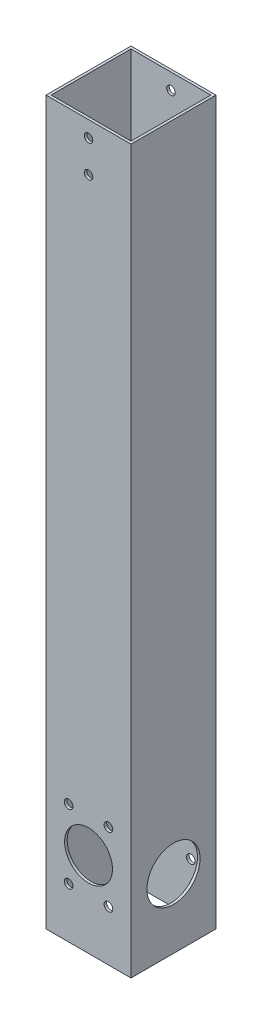
SolidWorks part; units mm, degrees
material "6061 Alloy"
ref_plane "Front Plane" through (0, 0, 0) normal (0, 0, 1) x (1, 0, 0)
ref_plane "Top Plane" through (0, 0, 0) normal (0, 1, 0) x (1, 0, 0)
ref_plane "Right Plane" through (0, 0, 0) normal (1, 0, 0) x (0, 0, -1)
sketch "Sketch1" plane through (0, 0, 0) normal (0, 1, 0) x (1, 0, 0)
  line L1 (25.4, 25.4) -> (-25.4, 25.4)
  line L2 (25.4, 25.4) -> (25.4, -25.4)
  line L3 (25.4, -25.4) -> (-25.4, -25.4)
  line L4 (-25.4, 25.4) -> (-25.4, -25.4)
  line L5 (25.4, 25.4) -> (-25.4, -25.4) construction
  line L6 (25.4, -25.4) -> (-25.4, 25.4) construction
  point P0 (0, 0)
  dimension "D1" = 50.8
extrude "Extrude-Thin1" add sketch "Sketch1" along normal blind 431.8 thin thin type one direction reverse wall 1.524
sketch "Sketch2" plane through (0, 0, 0) normal (0, 0, 1) x (1, 0, 0)
  line L0 (-36.2563, 68.2625) -> (38.5702, 68.2625) construction
  line L1 (-25.4, 0) -> (25.4, 0) construction
  line L2 (-25.4, 50.8) -> (25.4, 50.8) construction
  line L6 (25.4, 431.8) -> (25.4, 0) construction
  line L7 (-25.4, 431.8) -> (-25.4, 0) construction
  line L8 (-11.9062, 30.1778) -> (11.9063, 30.1778) construction
  line L9 (-11.9062, 71.4222) -> (11.9063, 71.4222) construction
  circle A0 centre (0, 50.8) radius 14.3002
  circle A1 centre (0, 50.8) radius 23.8125 construction
  circle A2 centre (-11.9062, 30.1778) radius 2.5908
  circle A3 centre (11.9063, 30.1778) radius 2.5908
  circle A4 centre (11.9063, 71.4222) radius 2.5908
  circle A5 centre (-11.9062, 71.4222) radius 2.5908
  point P11 (0, 50.8)
  dimension "D1" = 28.6004
  dimension "D3" = 17.4625
  dimension "D4" = 47.625
  dimension "D6" = 5.1816
  dimension "D2" = 50.8
  dimension "D5" = 60
extrude "Cut-Extrude1" cut sketch "Sketch2" along normal through all both and the other way through all
sketch "Sketch3" plane through (25.4, 0, 0) normal (1, 0, 0) x (0, 0, -1)
  line L0 (-25.4, 50.8) -> (25.4, 50.8) construction
  line L1 (-25.4, 65.1002) -> (-25.4, 36.4998) construction
  line L3 (25.4, 431.8) -> (25.4, 0) construction
  circle A0 centre (0, 41.275) radius 15.875
  point P9 (0, 50.8)
  dimension "D1" = 31.75
  dimension "D2" = 9.525
extrude "Cut-Extrude2" cut sketch "Sketch3" against normal up to surface (1.524 mm away) up to face at (23.876, 215.9, 0)
sketch "Sketch4" plane through (0, 0, 25.4) normal (0, 0, 1) x (1, 0, 0)
  line L0 (-25.4, 431.8) -> (25.4, 431.8) construction
  circle A0 centre (0, 422.275) radius 2.54
  circle A1 centre (0, 403.225) radius 2.54
  dimension "D1" = 5.08
  dimension "D2" = 9.525
  dimension "D3" = 28.575
hole_wizard "#10 Clearance Hole1" positions "Sketch5" profile "Sketch6" hole size "#10" standard "ANSI Inch" end condition through all
sketch "Sketch5" plane through (0, 0, 25.4) normal (0, 0, 1) x (1, 0, 0)
  point P0 (0, 403.225)
  point P3 (0, 422.275)
sketch "Sketch6" plane through (0, 403.225, 25.4) normal (1, 0, 0) x (0, -1, 0)
  line L0 (0, 0) -> (0, 50.8)
  line L1 (0, 50.8) -> (2.5527, 50.8)
  line L2 (2.5527, 50.8) -> (2.5527, 0)
  line L5 (2.5527, 0) -> (0, 0)
  line L11 (0, -6.35) -> (0, 107.95) construction
  dimension "Thru Hole Dia." = 5.1054
  dimension "Thru Hole Depth" = 50.8
